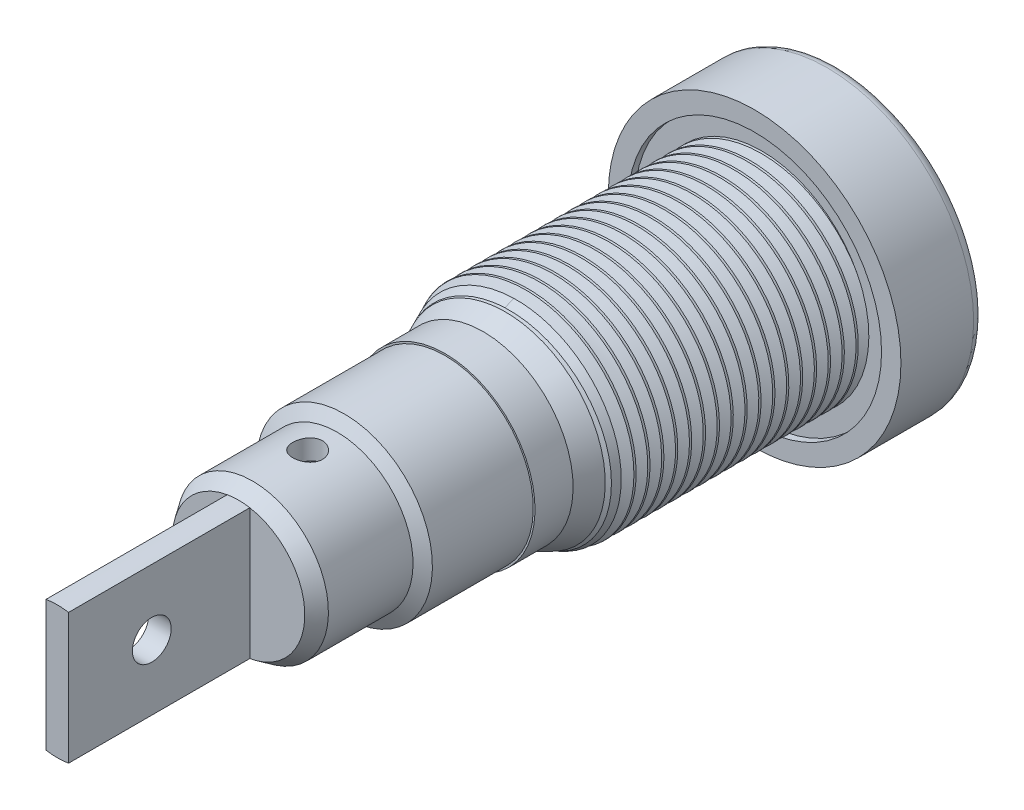
SolidWorks part; units mm, degrees
ref_plane "Front Plane" through (0, 0, 0) normal (0, 0, 1) x (1, 0, 0)
ref_plane "Top Plane" through (0, 0, 0) normal (0, 1, 0) x (1, 0, 0)
ref_plane "Right Plane" through (0, 0, 0) normal (1, 0, 0) x (0, 0, -1)
sketch "Sketch1" plane through (0, 0, 0) normal (1, 0, 0) x (0, 0, -1)
  line L0 (0, 0) -> (0, 5.2705)
  line L1 (0, 5.2705) -> (-2.9997, 5.2705)
  line L2 (-2.9997, 5.2705) -> (-2.9997, 3.8608)
  line L3 (-2.9997, 3.8608) -> (-11.3792, 3.8608)
  line L4 (-11.3792, 3.8608) -> (-12.7762, 3.2385)
  line L5 (-12.7762, 3.2385) -> (-14.1478, 3.2385)
  line L6 (-14.1478, 3.2385) -> (-14.1478, 3.175)
  line L7 (-14.1478, 3.175) -> (-17.78, 3.175)
  line L9 (-18.034, 2.7305) -> (-21.082, 2.7305)
  line L10 (-21.082, 2.7305) -> (-21.59, 2.3876)
  line L11 (-21.59, 2.3876) -> (-28.1178, 2.3876)
  line L12 (-28.1178, 2.3876) -> (-28.1178, 0)
  line L13 (0, 0) -> (-28.1178, 0)
  line L14 (-17.78, 3.175) -> (-18.034, 2.7305)
  dimension "D1" = 5.2705
  dimension "D2" = 2.9997
  dimension "D3" = 3.8608
  dimension "D4" = 11.3792
  dimension "D5" = 12.7762
  dimension "D6" = 3.2385
  dimension "D7" = 3.175
  dimension "D8" = 14.1478
  dimension "D9" = 17.78
  dimension "D10" = 21.082
  dimension "D11" = 28.1178
  dimension "D12" = 2.3876
  dimension "D13" = 2.7305
  dimension "D14" = 0.508
  dimension "D15" = 0.254
revolve "Revolve1" add sketch "Sketch1" angle 360 about L13
sketch "Sketch2" plane through (0, 0, 28.1178) normal (0, 0, 1) x (1, 0, 0)
  line L0 (0.4064, 2.3528) -> (0.4064, -2.3528)
  circle A0 centre (0, 0) radius 2.3876 construction
  arc A1 (0.4064, -2.3528) -> (0.4064, 2.3528) centre (0, 0) ccw
  dimension "D1" = 0.4064
extrude "Cut-Extrude1" cut sketch "Sketch2" along a picked direction on the side against the normal blind 6.5278
pattern_circular "CirPattern1" count 2 over 360 about axis through (0, 0, 21.59) along (0, 1, 0) of "Cut-Extrude1"
sketch "Sketch3" plane through (0, 0, 2.9997) normal (0, 0, 1) x (1, 0, 0)
  circle A0 centre (0, 0) radius 3.8608 construction
  circle A1 centre (0, 0) radius 3.8608
  circle A2 centre (0, 0) radius 4.572
  dimension "D1" = 9.144
extrude "Cut-Extrude2" cut sketch "Sketch3" against normal blind 0.254
thread "Thread1" pitch 0.5 start angle 0, offset 1, length 9.4996, pitch 0.5, diameter 7.7216
ref_plane "Plane1" through (-3.8608, 0, 12.3792) normal (0, -1, 0) x (-1, 0, 0)
sketch "Thread Profile1" plane through (-3.8608, 0, 12.3792) normal (0, -1, 0) x (-1, 0, 0)
  line L0 (0, 0) -> (0, 0.5) construction
  line L11 (0, 0) -> (0, 0.4203)
  line L12 (0, 0.4203) -> (-0.364, 0.2102)
  line L15 (-0.364, 0.2102) -> (0, 0)
  line L17 (-0.364, 0.2102) -> (0, 0.2102) construction
  point P2 (0, 0)
  dimension "D1" = 0.364
  dimension "Pitch" = 0.5
  dimension "Profile_Angle" = 60
sketch "Sketch6" plane through (-0.4064, 0, 0) normal (-1, 0, 0) x (0, 0, 1)
  line L0 (28.1178, -2.3528) -> (28.1178, 2.3528) construction
  circle A1 centre (25.1206, 0) radius 0.6985
  dimension "D1" = 1.397
  dimension "D2" = 2.9972
extrude "Cut-Extrude3" cut sketch "Sketch6" against normal blind 2.54
hole_wizard "#58 (0.042) Diameter Hole1" positions "3DSketch1" profile "Sketch7" hole size "#58" standard "ANSI Inch"
sketch3d "3DSketch1"
  point P0 (0, 2.7305, 19.1008)
  dimension "D1" = 2.4892
sketch "Sketch7" plane through (0, 2.7305, 19.1008) normal (1, 0, 0) x (0, 0, 1)
  line L0 (0, 0) -> (0, 4.3083)
  line L1 (0, 4.3083) -> (0.5334, 3.9878)
  line L2 (0.5334, 3.9878) -> (0.5334, 0)
  line L5 (0.5334, 0) -> (0, 0)
  line L10 (0, 4.3083) -> (-0.5334, 3.9878) construction
  line L11 (0, -6.35) -> (0, 107.95) construction
  dimension "Hole Dia." = 1.0668
  dimension "Hole Depth" = 3.9878
  dimension "Drill Angle" = 118
sketch "Sketch8" plane through (0, 0, 0) normal (0, 0, -1) x (-1, 0, 0)
  circle A0 centre (0, 0) radius 2.4765
extrude "Cut-Extrude4" cut sketch "Sketch8" against normal blind 3.175
hole_wizard "#21 (0.159) Diameter Hole1" positions "Sketch9" profile "Sketch10" hole size "#21" standard "ANSI Inch"
sketch "Sketch9" plane through (0, 0, 3.175) normal (0, 0, -1) x (-1, 0, 0)
  point P0 (0, 0)
sketch "Sketch10" plane through (0, 0, 3.175) normal (1, 0, 0) x (0, 1, 0)
  line L0 (0, 0) -> (0, 17.2661)
  line L1 (0, 17.2661) -> (2.0193, 16.0528)
  line L2 (2.0193, 16.0528) -> (2.0193, 0)
  line L5 (2.0193, 0) -> (0, 0)
  line L10 (0, 17.2661) -> (-2.0193, 16.0528) construction
  line L11 (0, -6.35) -> (0, 107.95) construction
  dimension "Hole Dia." = 4.0386
  dimension "Hole Depth" = 16.0528
  dimension "Drill Angle" = 118
chamfer "Chamfer1" distance 0.254 angle 45 1 edges at (0, 2.0193, 3.175)
fillet "Fillet1" radius 0.381 1 edges at (0, 5.2705, 0)
chamfer "Chamfer2" distance 0.254 angle 45 1 edges at (0, 2.4765, 0)
